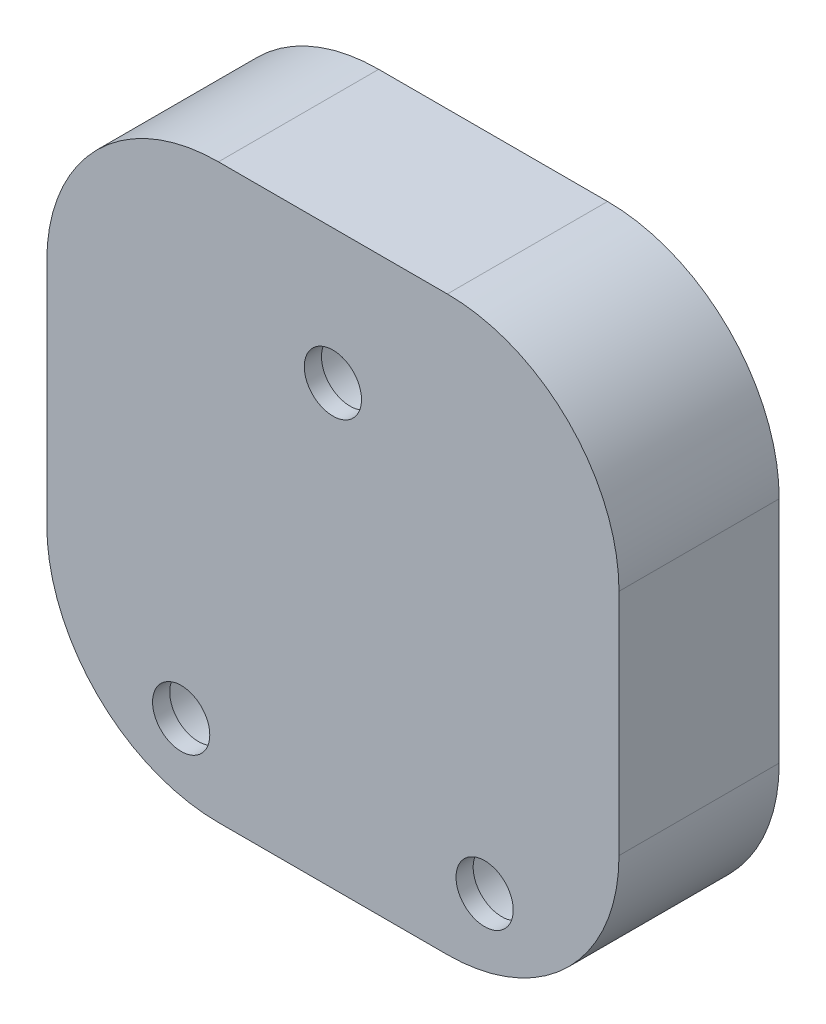
SolidWorks part; units mm, degrees
ref_plane "Front Plane" through (0, 0, 0) normal (0, 0, 1) x (1, 0, 0)
ref_plane "Top Plane" through (0, 0, 0) normal (0, 1, 0) x (1, 0, 0)
ref_plane "Right Plane" through (0, 0, 0) normal (1, 0, 0) x (0, 0, -1)
sketch "Sketch1" plane through (0, 0, 0) normal (0, 0, 1) x (1, 0, 0)
  line L0 (0, 64.0165) -> (0, 0) construction
  line L6 (-50, 87.5) -> (50, 87.5)
  line L7 (-50, 87.5) -> (-50, -12.5)
  line L8 (-50, -12.5) -> (50, -12.5)
  line L9 (50, 87.5) -> (50, -12.5)
  circle A0 centre (0, 0) radius 4
  circle A1 centre (26.5165, 64.0165) radius 4
  circle A2 centre (-26.5165, 64.0165) radius 4
  circle A3 centre (0, 64.0165) radius 8.1
  circle A4 centre (-26.5165, 0) radius 8.1
  circle A5 centre (26.5165, 0) radius 8.1
  point P4 (0, -12.5)
  point P10 (-50, 37.5)
  dimension "D3" = 8
  dimension "D4" = 16.2
  dimension "D5" = 16.2
  dimension "D6" = 16.2
  dimension "D1" = 100
  dimension "D2" = 100
extrude "Boss-Extrude1" add sketch "Sketch1" against normal blind 25
sketch "Sketch2" plane through (0, 0, 0) normal (0, 0, 1) x (1, 0, 0)
  line L4 (-50, 87.5) -> (-50, -12.5)
  line L5 (-50, -12.5) -> (50, -12.5)
  line L6 (50, -12.5) -> (50, 87.5)
  line L7 (50, 87.5) -> (-50, 87.5)
  line L8 (-50, 87.5) -> (-50, -12.5)
  line L9 (-50, -12.5) -> (50, -12.5)
  line L10 (50, -12.5) -> (50, 87.5)
  line L11 (50, 87.5) -> (-50, 87.5)
  circle A0 centre (0, 64.0165) radius 5
  circle A1 centre (26.5165, 0) radius 5
  circle A2 centre (-26.5165, 0) radius 5
  dimension "D2" = 10
  dimension "D3" = 10
  dimension "D4" = 10
  dimension "D1" = 0
extrude "Boss-Extrude2" add sketch "Sketch2" along normal blind 3
fillet "Fillet1" radius 30 4 edges at (50, 87.5, -11) (-50, 87.5, -11) (50, -12.5, -11) (-50, -12.5, -11)
fillet "Fillet2" radius 3 3 edges at (34.6165, 0, -25) (-18.4165, 0, -25) (8.1, 64.0165, -25)
sketch "Sketch3" plane through (0, 0, -25) normal (0, 0, -1) x (-1, 0, 0)
  circle A0 centre (0, 37.5) radius 6
  dimension "D1" = 12
extrude "Cut-Extrude1" cut sketch "Sketch3" against normal blind 10
fillet "Fillet3" radius 3 1 edges at (-6, 37.5, -25)
